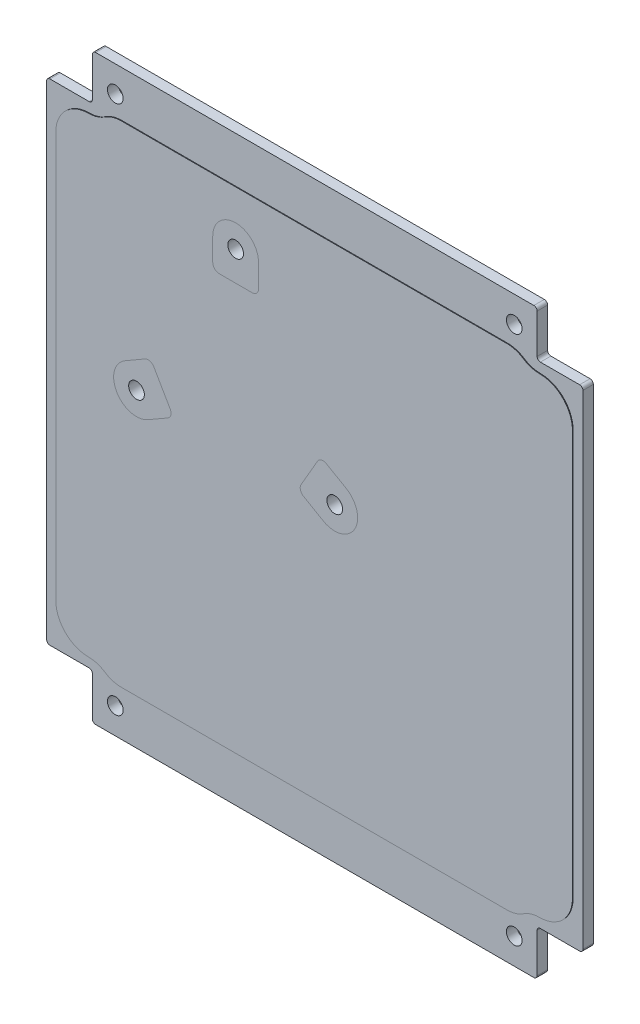
SolidWorks part; units mm, degrees
material "PET"
ref_plane "Front Plane" through (0, 0, 0) normal (0, 0, 1) x (1, 0, 0)
ref_plane "Top Plane" through (0, 0, 0) normal (0, 1, 0) x (1, 0, 0)
ref_plane "Right Plane" through (0, 0, 0) normal (1, 0, 0) x (0, 0, -1)
sketch "Sketch1" plane through (0, 0, 0) normal (0, 0, 1) x (1, 0, 0)
  line L0 (-34, 44) -> (-34, 38)
  line L1 (-33.5, -44.5) -> (33.5, -44.5)
  line L2 (-41, 37) -> (-41, -37)
  line L3 (-33.5, 44.5) -> (33.5, 44.5)
  line L4 (41, -37) -> (41, 37)
  line L5 (34, -44) -> (34, -38)
  line L6 (34.5, -37.5) -> (40.5, -37.5)
  line L7 (-34.5, 37.5) -> (-40.5, 37.5)
  line L8 (34, 44) -> (34, 38)
  line L9 (34.5, 37.5) -> (40.5, 37.5)
  line L10 (-40.5, -37.5) -> (-34.5, -37.5)
  line L11 (-34, -38) -> (-34, -44)
  line L12 (-34.5, -38) -> (34.5, 38) construction
  line L13 (34.5, -38) -> (-34.5, 38) construction
  arc A0 (-33.5, 44.5) -> (-34, 44) centre (-33.5, 44) ccw
  arc A1 (33.5, 44.5) -> (34, 44) centre (33.5, 44) cw
  arc A2 (34, 38) -> (34.5, 37.5) centre (34.5, 38) ccw
  arc A3 (40.5, 37.5) -> (41, 37) centre (40.5, 37) cw
  arc A4 (33.5, -44.5) -> (34, -44) centre (33.5, -44) ccw
  arc A5 (34.5, -37.5) -> (34, -38) centre (34.5, -38) ccw
  arc A6 (40.5, -37.5) -> (41, -37) centre (40.5, -37) ccw
  arc A7 (-34, -44) -> (-33.5, -44.5) centre (-33.5, -44) ccw
  arc A8 (-34, -38) -> (-34.5, -37.5) centre (-34.5, -38) ccw
  arc A9 (-41, -37) -> (-40.5, -37.5) centre (-40.5, -37) ccw
  arc A10 (-40.5, 37.5) -> (-41, 37) centre (-40.5, 37) ccw
  arc A11 (-34.5, 37.5) -> (-34, 38) centre (-34.5, 38) ccw
  point P0 (0, 0)
  dimension "D4" = 0.5
  dimension "D1" = 7
  dimension "D2" = 7
  dimension "D3" = 7
  dimension "D5" = 7
  dimension "D6" = 7
  dimension "D7" = 7
  dimension "D8" = 7
  dimension "D9" = 7
  dimension "D10" = 89
  dimension "D11" = 82
extrude "Boss-Extrude1" add sketch "Sketch1" along normal blind 1.6
sketch "Esboço1" plane through (0, 0, 1.6) normal (0, 0, 1) x (1, 0, 0)
  line L0 (11.8117, 0) -> (-11.978, 0) construction
  line L1 (-29.5, -37.5) -> (29.5, -37.5)
  line L2 (0, 10.1561) -> (0, -5.0161) construction
  line L3 (-29.5, 37.5) -> (29.5, 37.5)
  line L5 (-29.5, -32.5) -> (29.5, 32.5) construction
  line L6 (-29.5, 32.5) -> (29.5, -32.5) construction
  line L8 (-39.5, -31) -> (-39.5, 31)
  line L10 (39.5, -31) -> (39.5, 31)
  line L11 (-39.5, -36) -> (39.5, 36) construction
  line L12 (-39.5, 36) -> (39.5, -36) construction
  arc A0 (-34.5, 36) -> (-32, 36.75) centre (-34.5, 40.5417) ccw
  arc A1 (-29.5, 37.5) -> (-32, 36.75) centre (-29.5, 32.9583) ccw
  arc A2 (-29.5, -37.5) -> (-32, -36.75) centre (-29.5, -32.9583) cw
  arc A3 (-34.5, -36) -> (-32, -36.75) centre (-34.5, -40.5417) cw
  arc A4 (34.5, 36) -> (39.5, 31) centre (34.5, 31) cw
  arc A5 (34.5, -36) -> (39.5, -31) centre (34.5, -31) ccw
  arc A6 (-34.5, -36) -> (-39.5, -31) centre (-34.5, -31) cw
  arc A7 (-39.5, 31) -> (-34.5, 36) centre (-34.5, 31) cw
  arc A8 (29.5, -37.5) -> (32, -36.75) centre (29.5, -32.9583) ccw
  arc A9 (34.5, -36) -> (32, -36.75) centre (34.5, -40.5417) ccw
  arc A10 (29.5, 37.5) -> (32, 36.75) centre (29.5, 32.9583) cw
  arc A11 (34.5, 36) -> (32, 36.75) centre (34.5, 40.5417) cw
  point P0 (0, 0)
  point P1 (0, 0)
  dimension "D2" = 5
  dimension "D3" = 75
  dimension "D5" = 79
extrude "Boss-Extrude2" add sketch "Esboço1" along normal blind 0.1
hole_wizard "M2 Hole1-FixingStructure" positions "Sketch3" profile "Sketch2" hole size "M2" standard "DIN"
sketch "Sketch3" plane through (0, 0, 0) normal (0, 0, -1) x (-1, 0, 0)
  line L0 (-33.5, 44.5) -> (33.5, 44.5) construction
  line L1 (33.5, -44.5) -> (-33.5, -44.5) construction
  line L2 (-41, -37) -> (-41, 37) construction
  line L3 (41, 37) -> (41, -37) construction
  point P0 (-30.5, 40.5)
  point P2 (30.5, 40.5)
  point P4 (-30.5, -40.5)
  point P6 (30.5, -40.5)
  dimension "D1" = 4
  dimension "D2" = 4
  dimension "D3" = 10.5
  dimension "D4" = 10.5
sketch "Sketch2" plane through (30.5, 40.5, 0) normal (1, 0, 0) x (0, 1, 0)
  line L0 (0, 0) -> (0, 200.721)
  line L1 (0, 200.721) -> (1.2, 200)
  line L2 (1.2, 200) -> (1.2, 0)
  line L5 (1.2, 0) -> (0, 0)
  line L10 (0, 200.721) -> (-1.2, 200) construction
  line L11 (0, -6.35) -> (0, 107.95) construction
  dimension "Hole Dia." = 2.4
  dimension "Hole Depth" = 200
  dimension "Drill Angle" = 118
sketch "Sketch4" plane through (0, 0, 1.7) normal (0, 0, 1) x (1, 0, 0)
  circle A0 centre (-27.1554, 3) radius 1.2 construction
  circle A1 centre (-12, 29.25) radius 1.2 construction
  circle A2 centre (3.1554, 3) radius 1.2 construction
  circle A3 centre (-27.1554, 3) radius 1.2
  circle A4 centre (-12, 29.25) radius 1.2
  circle A5 centre (3.1554, 3) radius 1.2
extrude "Cut-Extrude1" cut sketch "Sketch4" against normal up to surface (1.7 mm away) up to face at (29.3, 40.5, 0)
sketch "Sketch5" plane through (0, 0, 1.7) normal (0, 0, 1) x (1, 0, 0)
  line L5 (-8.5, 29.25) -> (-8.5, 25.75)
  line L6 (-28.9054, 6.0311) -> (-26.7404, 7.2811)
  line L7 (-23.2404, 1.2189) -> (-25.4054, -0.0311)
  line L8 (-28.9054, 6.0311) -> (-25.8744, 7.7811)
  line L9 (-22.3744, 1.7189) -> (-25.4054, -0.0311)
  line L10 (-24.5083, 7.4151) -> (-22.0083, 3.0849)
  line L11 (-24.5083, 7.4151) -> (-22.0083, 3.0849)
  line L12 (-15.5, 25.75) -> (-15.5, 29.25)
  line L13 (-9.5, 24.75) -> (-14.5, 24.75)
  line L14 (1.4054, -0.0311) -> (-1.6256, 1.7189)
  line L15 (1.8744, 7.7811) -> (4.9054, 6.0311)
  line L16 (-1.9917, 3.0849) -> (0.5083, 7.4151)
  circle A0 centre (-12, 11.75) radius 4.4 construction
  arc A3 (-25.8744, 7.7811) -> (-24.5083, 7.4151) centre (-25.3744, 6.9151) cw
  arc A4 (-28.9054, 6.0311) -> (-25.4054, -0.0311) centre (-27.1554, 3) ccw
  arc A5 (-28.9054, 6.0311) -> (-25.4054, -0.0311) centre (-27.1554, 3) ccw
  arc A6 (-22.3744, 1.7189) -> (-22.0083, 3.0849) centre (-22.8744, 2.5849) ccw
  arc A7 (-8.5, 25.75) -> (-9.5, 24.75) centre (-9.5, 25.75) cw
  arc A8 (-8.5, 29.25) -> (-15.5, 29.25) centre (-12, 29.25) ccw
  arc A9 (-15.5, 25.75) -> (-14.5, 24.75) centre (-14.5, 25.75) ccw
  arc A10 (-1.6256, 1.7189) -> (-1.9917, 3.0849) centre (-1.1256, 2.5849) cw
  arc A11 (1.4054, -0.0311) -> (4.9054, 6.0311) centre (3.1554, 3) ccw
  arc A12 (1.8744, 7.7811) -> (0.5083, 7.4151) centre (1.3744, 6.9151) ccw
  point P0 (-12, 11.75)
  point P36 (-12, 11.75)
  dimension "D3" = 1
  dimension "D1" = 1
  dimension "D2" = 1
  dimension "D4" = 3
split line "Split Line1"
